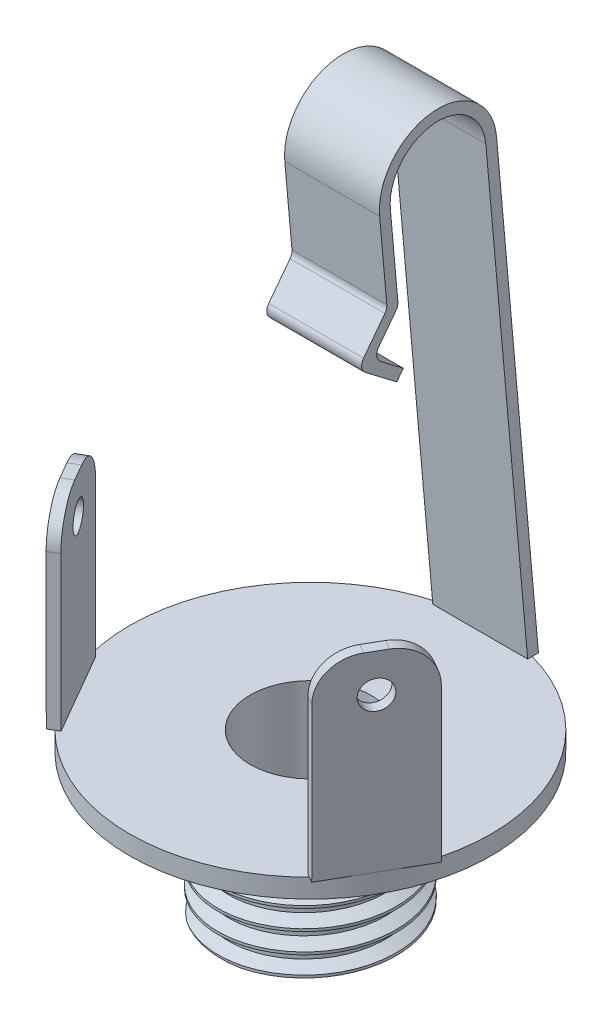
SolidWorks part; units mm, degrees
material "Nickel silver 65-12, UNS C75700"
ref_plane "Front Plane" through (0, 0, 0) normal (0, 0, 1) x (1, 0, 0)
ref_plane "Top Plane" through (0, 0, 0) normal (0, 1, 0) x (1, 0, 0)
ref_plane "Right Plane" through (0, 0, 0) normal (1, 0, 0) x (0, 0, -1)
sketch "Sketch1" plane through (0, 0, 0) normal (0, 1, 0) x (1, 0, 0)
  line L0 (0, 0) -> (0, 28.1269) construction
  line L1 (11.8439, 6.8381) -> (-11.8439, -6.8381) construction
  line L2 (0, 0) -> (-17.9216, 10.347) construction
  circle A0 centre (0, 0) radius 9.525
  circle A1 centre (0, 0) radius 4.699
  circle A2 centre (0, 0) radius 3.175
  point P11 (0, 0)
  dimension "D1" = 19.05
  dimension "D2" = 9.398
  dimension "D3" = 6.35
  dimension "D4" = 60
  dimension "D5" = 60
extrude "Boss-Extrude2" add sketch "Sketch1" against normal blind 7.112 contours A1 A2 region at (-4.5661, 0, 0)
extrude "Boss-Extrude3" add sketch "Sketch1<5>" along normal blind 1 contours A0 A1 | A1 A2 region at (-9.2556, 0, 0) region at (-4.5661, 0, 0)
sketch "Sketch1<5>" plane through (0, 0, 0) normal (0, 1, 0) x (1, 0, 0) same geometry as "Sketch1"
sketch "Sketch2" plane through (0, 0, 0) normal (1, 0, 0) x (0, 0, -1)
  line L6 (9.525, 1) -> (8.9553, 1)
  line L15 (9.525, 1) -> (7.3147, 25.6761)
  line L16 (1.1503, 25.1239) -> (1.529, 20.8954)
  line L17 (1.429, 20.5481) -> (0.3027, 19.067)
  line L18 (0.398, 18.3663) -> (2.0541, 17.1069)
  line L19 (8.9553, 1) -> (6.7496, 25.6255)
  line L20 (1.7154, 25.1745) -> (2.1138, 20.727)
  line L21 (2.0138, 20.3797) -> (1.0977, 19.1752)
  line L22 (1.1931, 18.4745) -> (2.3976, 17.5585)
  line L24 (8.9599, 0.9494) -> (6.7496, 25.6255) construction
  line L25 (2.0541, 17.1069) -> (2.3976, 17.5585)
  line L26 (9.525, 1) -> (-9.525, 1) construction
  line L27 (-4.699, -7.112) -> (4.699, -7.112) construction
  line L28 (2.3976, 17.5585) -> (2.1311, 20.5339) construction
  line L29 (1.5463, 20.7024) -> (0, 18.669) construction
  line L30 (0, 18.669) -> (2.0541, 17.1069) construction
  line L31 (1.7154, 25.1745) -> (2.1311, 20.5339) construction
  line L32 (2.1311, 20.5339) -> (0.7951, 18.7772) construction
  line L33 (1.1503, 25.1239) -> (1.5463, 20.7024) construction
  line L34 (0.7951, 18.7772) -> (2.3976, 17.5585) construction
  arc A0 (7.3147, 25.6761) -> (1.1503, 25.1239) centre (4.2325, 25.4) ccw
  arc A1 (6.7496, 25.6255) -> (1.7154, 25.1745) centre (4.2325, 25.4) ccw
  arc A2 (0.3027, 19.067) -> (0.398, 18.3663) centre (0.7007, 18.7643) ccw
  arc A3 (2.1138, 20.727) -> (2.0138, 20.3797) centre (1.6158, 20.6824) cw
  arc A4 (1.529, 20.8954) -> (1.429, 20.5481) centre (1.031, 20.8508) cw
  arc A5 (1.0977, 19.1752) -> (1.1931, 18.4745) centre (1.4957, 18.8725) ccw
  point P22 (0, 18.669)
  dimension "D3" = 0.5
  dimension "D4" = 0.5
  dimension "D5" = 0.5
  dimension "D6" = 3.0946
  dimension "D7" = 2.5272
  dimension "D2" = 25.781
  dimension "D1" = 25.4
  dimension "D8" = 24.6255
extrude "Boss-Extrude4" add sketch "Sketch2" along normal blind 2.5 and the other way blind 2.5
ref_axis "Axis1" through (0, -7.112, 0) along (0, 1, 0)
ref_plane "Plane1" through (0, 0, 0) normal (0.5, 0, 0.866) x (0, 1, 0)
ref_plane "Plane2" through (0, 0, 0) normal (0.5, 0, -0.866) x (0, 1, 0)
sketch "Sketch3" plane through (0, 0, 0) normal (0.5, 0, 0.866) x (0, 1, 0)
  line L0 (1, 9.525) -> (11.1065, 9.5319)
  line L4 (11.1065, 9.5319) -> (11.1065, 8.9619)
  line L5 (11.1065, 8.9619) -> (1, 8.955)
  line L6 (1, 8.955) -> (1, 9.525)
  line L7 (1, -6.6427) -> (1, -6.7606) construction
  dimension "D1" = 0.57
extrude "Boss-Extrude5" add sketch "Sketch3" along normal blind 2.5 and the other way blind 2.5
fillet "Fillet1" radius 2 2 edges at (-6.758, 11.1065, 6.7885) (-9.258, 11.1065, 2.4584)
sketch "Sketch4" plane through (-8.2483, -0.0065, 4.7622) normal (-0.866, -0.0007, 0.5) x (0.5, 0.0004, 0.866)
  line L0 (-0.4956, 11.1132) -> (0.5044, 11.1128) construction
  circle A0 centre (0.0044, 9.114) radius 0.75
  point P6 (0.0044, 11.113)
  dimension "D1" = 1.5
extrude "Cut-Extrude1" cut sketch "Sketch4" against normal up to next
mirror "Mirror1" about plane through (0, 0, 0) normal (1, 0, 0) of "Fillet1", "Cut-Extrude1", "Boss-Extrude5"
thread "Thread1" pitch 1.0583 method cut trim with end face yes profile "Thread Profile1" start angle 0, offset 0, length 0, pitch 1.0583, diameter 9.398
ref_plane "Plane3" through (-4.699, 0, 0) normal (0, 0, 1) x (-1, 0, 0)
sketch "Thread Profile1" plane through (-4.699, 0, 0) normal (0, 0, 1) x (-1, 0, 0)
  line L0 (0, 0) -> (0, 1.0583) construction
  line L11 (0, 0) -> (0, 0.926)
  line L12 (0, 0.926) -> (-0.5728, 0.5953)
  line L13 (-0.5728, 0.5953) -> (-0.5728, 0.3307)
  line L15 (-0.5728, 0.3307) -> (0, 0)
  line L17 (-0.5728, 0.463) -> (0, 0.463) construction
  point P2 (0, 0)
  dimension "Pitch" = 1.0583
  dimension "Profile_Angle" = 60
  dimension "Profile_Land" = 0.2646
  dimension "Profile_Height" = 0.5728
